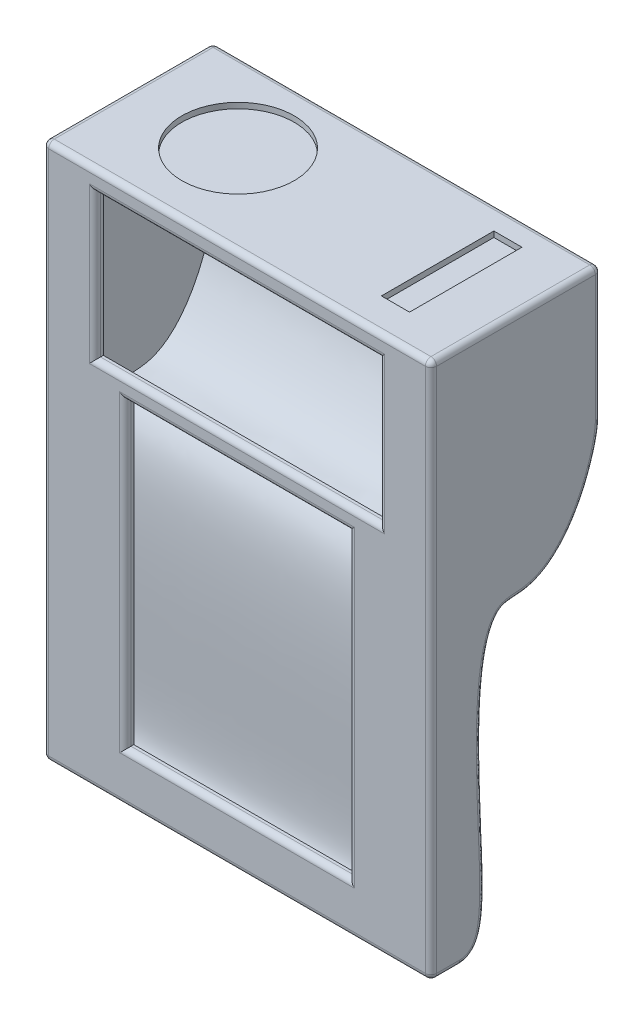
SolidWorks part; units mm, degrees
note: The reader was unsure of these and kept them because the rebuilt part matched: shared geometry of "Sketch1<3>", "Sketch1<4>", "Sketch1<5>", "Sketch1<6>", "Sketch3<3>".
ref_plane "Front Plane" through (0, 0, 0) normal (0, 0, 1) x (1, 0, 0)
ref_plane "Top Plane" through (0, 0, 0) normal (0, 1, 0) x (1, 0, 0)
ref_plane "Right Plane" through (0, 0, 0) normal (1, 0, 0) x (0, 0, -1)
sketch "Sketch1" plane through (0, 0, 0) normal (0, 0, 1) x (1, 0, 0)
  line L1 (49.8546, 107.7175) -> (-16.1454, 107.7175)
  line L2 (49.8546, 107.7175) -> (49.8546, 15.2175)
  line L3 (49.8546, 15.2175) -> (-16.1454, 15.2175)
  line L4 (-16.1454, 107.7175) -> (-16.1454, 15.2175)
  line L5 (16.8546, 15.2175) -> (16.8546, 107.7175) construction
  line L6 (49.8546, 61.4675) -> (-16.1454, 61.4675) construction
  line L22 (-2.0054, 75.1221) -> (-2.0054, 76.1221) construction
  line L23 (36.7146, 76.1221) -> (-3.0054, 76.1221)
  line L24 (36.7146, 76.1221) -> (36.7146, 22.5121)
  line L25 (36.7146, 22.5121) -> (-3.0054, 22.5121)
  line L26 (-3.0054, 76.1221) -> (-3.0054, 22.5121)
  line L27 (16.8546, 22.5121) -> (16.8546, 76.1221) construction
  line L28 (36.7146, 49.3171) -> (-3.0054, 49.3171) construction
  line L29 (42.1296, 105.4705) -> (-8.4204, 105.4705)
  line L30 (42.1296, 105.4705) -> (42.1296, 79.7655)
  line L31 (42.1296, 79.7655) -> (-8.4204, 79.7655)
  line L32 (-8.4204, 105.4705) -> (-8.4204, 79.7655)
  line L33 (16.8546, 79.7655) -> (16.8546, 105.4705) construction
  line L34 (42.1296, 92.618) -> (-8.4204, 92.618) construction
  line L35 (-2.0054, 75.1221) -> (-3.0054, 75.1221) construction
  line L36 (35.7146, 23.5121) -> (36.7146, 23.5121) construction
  line L37 (35.7146, 23.5121) -> (35.7146, 22.5121) construction
  line L38 (-7.4204, 80.7655) -> (-7.4204, 79.7655) construction
  line L39 (-7.4204, 80.7655) -> (-8.4204, 80.7655) construction
  line L40 (41.1296, 104.4705) -> (41.1296, 105.4705) construction
  line L41 (41.1296, 104.4705) -> (42.1296, 104.4705) construction
  line L42 (-15.6454, 85.7175) -> (-16.1454, 85.7175) construction
  line L43 (49.3546, 15.7175) -> (49.3546, 15.2175) construction
  line L44 (-10.8954, 107.2175) -> (-10.8954, 107.7175) construction
  line L45 (-3.0054, 22.5121) -> (-3.0054, 21.0121) construction
  line L46 (49.3546, 15.7175) -> (49.8546, 15.7175) construction
  line L47 (38.2146, 77.6221) -> (-4.5054, 77.6221)
  line L48 (38.2146, 77.6221) -> (38.2146, 21.0121)
  line L49 (38.2146, 21.0121) -> (-4.5054, 21.0121)
  line L50 (-4.5054, 77.6221) -> (-4.5054, 21.0121)
  line L51 (38.2146, 77.6221) -> (-4.5054, 21.0121) construction
  line L52 (38.2146, 21.0121) -> (-4.5054, 77.6221) construction
  line L53 (-9.9204, 106.9705) -> (43.6296, 106.9705)
  line L54 (-9.9204, 106.9705) -> (-9.9204, 78.2655)
  line L55 (-9.9204, 78.2655) -> (43.6296, 78.2655)
  line L56 (43.6296, 106.9705) -> (43.6296, 78.2655)
  line L57 (-9.9204, 106.9705) -> (43.6296, 78.2655) construction
  line L58 (-9.9204, 78.2655) -> (43.6296, 106.9705) construction
  line L59 (-3.0054, 22.5121) -> (-4.5054, 22.5121) construction
  line L60 (-8.4204, 79.7655) -> (-8.4204, 78.2655) construction
  line L61 (-8.4204, 79.7655) -> (-9.9204, 79.7655) construction
  line L62 (49.8546, 15.2175) -> (49.8546, 13.7175) construction
  line L63 (-17.6454, 109.2175) -> (51.3546, 109.2175)
  line L64 (-17.6454, 109.2175) -> (-17.6454, 13.7175)
  line L65 (-17.6454, 13.7175) -> (51.3546, 13.7175)
  line L66 (51.3546, 109.2175) -> (51.3546, 13.7175)
  line L67 (-17.6454, 109.2175) -> (51.3546, 13.7175) construction
  line L68 (-17.6454, 13.7175) -> (51.3546, 109.2175) construction
  line L69 (49.8546, 15.2175) -> (51.3546, 15.2175) construction
  point P0 (16.8546, 61.4675)
  point P4 (0, 0)
  point P5 (49.3546, 15.7175)
  point P31 (16.8546, 92.618)
  point P39 (16.8546, 49.3171)
  point P59 (16.8546, 49.3171)
  point P68 (16.8546, 92.618)
  point P79 (16.8546, 61.4675)
  dimension "D6" = 1
  dimension "D7" = 1
  dimension "D8" = 0.5
  dimension "D9" = 1.5
  dimension "D10" = 1.5
  dimension "D11" = 1.5
extrude "Boss-Extrude1" add sketch "Sketch1" along normal blind 1.5
extrude "Boss-Extrude2" add sketch "Sketch1<3>" against normal up to surface (0.0005 mm away) contours L47 L50 L49 L48 L26 L23 L24 L25
sketch "Sketch1<3>" plane through (0, 0, 0) normal (0, 0, 1) x (1, 0, 0) same geometry as "Sketch1"
extrude "Boss-Extrude3" add sketch "Sketch1<4>" against normal up to surface (0.0005 mm away) contours L56 L53 L54 L55 L32 L29 L30 L31
sketch "Sketch1<4>" plane through (0, 0, 0) normal (0, 0, 1) x (1, 0, 0) same geometry as "Sketch1"
extrude "Boss-Extrude4" add sketch "Sketch1<5>" along normal up to surface and the other way up to surface contours L66 L63 L64 L65 L4 L1 L2 L3
sketch "Sketch1<5>" plane through (0, 0, 0) normal (0, 0, 1) x (1, 0, 0) same geometry as "Sketch1"
extrude "Boss-Extrude5" add sketch "Sketch1<6>" against normal blind 1.5 from surface at -27.2345 contours L64 L65 L66 L63 starting at face at (16.8546, 61.4675, -27.2345)
sketch "Sketch1<6>" plane through (0, 0, 0) normal (0, 0, 1) x (1, 0, 0) same geometry as "Sketch1"
sketch "Sketch2" plane through (0, 109.2175, 0) normal (0, 1, 0) x (1, 0, 0)
  line L0 (36.6046, 24.4345) -> (36.6046, 4.4345) construction
  line L1 (36.6046, 4.4345) -> (41.6046, 4.4345)
  line L2 (36.6046, 4.4345) -> (36.6046, 24.4345)
  line L3 (36.6046, 24.4345) -> (41.6046, 24.4345)
  line L4 (41.6046, 4.4345) -> (41.6046, 24.4345)
  line L5 (36.6046, 4.4345) -> (41.6046, 4.4345) construction
  circle A0 centre (1.1046, 14.4345) radius 10
  circle A1 centre (1.1046, 14.4345) radius 10 construction
extrude "Cut-Extrude1" cut sketch "Sketch2" against normal blind 1
sketch "Sketch3" plane through (-17.6454, 0, 0) normal (-1, 0, 0) x (0, 0, 1)
  line L0 (-27.2345, 15.2175) -> (-27.2345, 107.7175) construction
  line L1 (0, 15.2175) -> (-27.2345, 15.2175) construction
  line L2 (16.0109, 15.2175) -> (14.7193, 15.2175) construction
  line L3 (-27.2345, 172.1688) -> (-27.2345, 209.241) construction
  line L4 (-27.2345, 85.7175) -> (-28.7345, 85.7175)
  line L5 (-3.6014, 15.2175) -> (-3.6014, 13.7175)
  line L6 (-3.6014, 13.7175) -> (-28.7345, 13.6765)
  line L7 (-28.7345, 13.6765) -> (-28.7345, 85.7175)
  spline S0 degree 3 poles (-27.2345, 85.7175) (-27.2345, 81.8578) (-22.3894, 65.8842) (-6.0892, 67.5425) (-5.6256, 31.3495) (-7.9373, 15.2175) (-3.6014, 15.2175) knots 0 0 0 0 0.343299 0.407295 0.639964 1 1 1 1
  spline S1 degree 1 poles (-28.7345, 85.7175) (-3.6014, 13.7175) knots 0 0 1 1 construction
  spline S2 degree 3 poles (-28.7345, 85.7175) (-28.7345, 85.483) (-28.7134, 85.032) (-28.5994, 83.9895) (-28.3274, 82.5032) (-27.7966, 80.4521) (-26.8134, 77.4806) (-25.4125, 74.3275) (-23.566, 71.3599) (-21.9419, 69.3205) (-20.0574, 67.567) (-18.238, 66.442) (-16.642, 65.8201) (-14.9123, 65.4103) (-13.2872, 65.3679) (-12.056, 65.2067) (-11.4002, 65.0011) (-10.8868, 64.6649) (-10.134, 63.8618) (-9.2496, 62.1602) (-8.178, 58.2031) (-7.542, 51.6263) (-7.5445, 44.3011) (-7.6901, 38.7949) (-7.8746, 33.6769) (-8.1204, 27.9939) (-8.2092, 23.3521) (-8.0731, 20.2806) (-7.8321, 18.2885) (-7.3963, 16.5838) (-6.6585, 15.1133) (-5.3425, 13.9598) (-4.171, 13.7175) (-3.6014, 13.7175) knots 0 0 0 0 0.015625 0.03125 0.0625 0.09375 0.125 0.1875 0.21875 0.25 0.28125 0.3125 0.328125 0.34375 0.375 0.390625 0.40625 0.421875 0.4375 0.46875 0.5 0.5625 0.625 0.65625 0.6875 0.75 0.8125 0.84375 0.875 0.90625 0.9375 0.96875 1 1 1 1
  point P2 (-15.4011, 66.9649)
  point P4 (0, 0)
  point P6 (-7.5603, 15.2175)
  point P7 (0, 0)
  point P12 (0, 0)
  point P15 (-15.4011, 66.9649)
  point P16 (0, 0)
  point P17 (0, 0)
  point P19 (-13.3974, 45.0244)
  point P20 (-10.2255, 63.9705)
  point P21 (-12.6024, 66.7041)
  point P27 (0, 0)
  point P28 (-11.0291, 44.8077)
  point P29 (0, 0)
  line M3 (-28.7345, 109.2175) -> (-28.7345, 13.7175)
  line M4 (-28.7345, 13.7175) -> (1.5, 13.7175)
  dimension "D1" = 1.5
extrude "Boss-Extrude6" add sketch "Sketch3" against normal up to surface (69 mm away) contours L4 S2 L5 S0 up to face at (51.3546, 61.4675, -13.6172)
extrude "Cut-Extrude2" cut sketch "Sketch3<3>" against normal up to next (69 mm away) contours S2 M3 M4
sketch "Sketch3<3>" plane through (-17.6454, 0, 0) normal (-1, 0, 0) x (0, 0, 1) same geometry as "Sketch3"
fillet "Fillet1" radius 1 21 edges at (51.3546, 97.4675, -28.7345) (-17.6454, 13.7175, -1.0507) (16.8546, 105.4705, 1.5) (42.1296, 92.618, 1.5) (16.8546, 79.7655, 1.5) (-8.4204, 92.618, 1.5) (16.8546, 76.1221, 1.5) (36.7146, 49.3171, 1.5) (16.8546, 22.5121, 1.5) (-3.0054, 49.3171, 1.5) (-17.6454, 109.2175, -13.6172) (16.8546, 109.2175, 1.5) (16.8546, 109.2175, -28.7345) (51.3546, 109.2175, -13.6172) (51.3546, 13.7175, -1.0507) (51.3546, 61.4675, 1.5) (-17.6454, 61.4675, 1.5) (16.8546, 13.7175, 1.5) (-17.6454, 97.4675, -28.7345)
